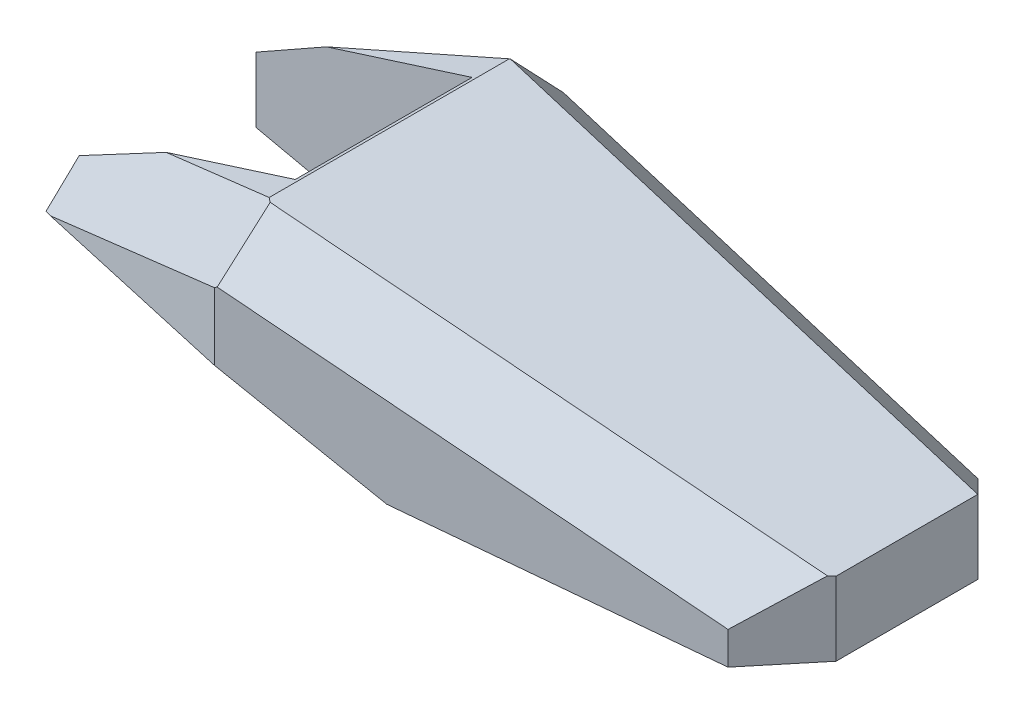
SolidWorks part; units mm, degrees
ref_plane "Front Plane" through (0, 0, 0) normal (0, 0, 1) x (1, 0, 0)
ref_plane "Top Plane" through (0, 0, 0) normal (0, 1, 0) x (1, 0, 0)
ref_plane "Right Plane" through (0, 0, 0) normal (1, 0, 0) x (0, 0, -1)
sketch "Sketch1" plane through (0, 0, 0) normal (0, 0, 1) x (1, 0, 0)
  line L0 (75, 0) -> (-75, 0)
  line L1 (-75, 0) -> (-75, 20)
  line L2 (-75, 20) -> (-30.2416, 34.2396)
  line L3 (-30.2416, 34.2396) -> (75, 15)
  line L4 (75, 15) -> (75, 0)
  point P0 (-30.2416, 34.2396)
  point P4 (0, 0)
extrude "Boss-Extrude1" add sketch "Sketch1" along normal mid plane 70
sketch "Sketch3" plane through (0, 0, 0) normal (0, -1, 0) x (1, 0, 0)
  line L0 (75, -25) -> (75, -35)
  line L1 (75, 35) -> (75, -35) construction
  line L2 (-75, 35) -> (-30.49, 35) construction
  line L3 (-75, 35) -> (75, 35) construction
  line L4 (-30.49, 35) -> (75, 25)
  line L5 (75, 35) -> (-30.49, 35)
  line L6 (75, 25) -> (75, 35)
  line L7 (-75, 35) -> (-75, 25)
  line L8 (-75, 35) -> (-75, -35) construction
  line L9 (-75, 25) -> (-30.49, 35)
  line L10 (-75, 35) -> (-30.49, 35)
  line L11 (0, 0) -> (-75, 0) construction
  line L13 (-75, 18) -> (-31, 18)
  line L14 (-31, 18) -> (-31, -18)
  line L15 (75, -35) -> (-30.49, -35)
  line L16 (-75, -35) -> (-30.49, -35) construction
  line L17 (-75, -18) -> (-31, -18)
  line L19 (-75, -35) -> (-30.49, -35)
  line L20 (-75, -25) -> (-30.49, -35)
  line L21 (-75, -35) -> (-75, -25)
  line L22 (-30.49, -35) -> (75, -25)
  line L23 (-75, 18) -> (-75, -18)
  point P5 (75, 0.2276)
  point P21 (-31, 0)
  point P24 (75, -0.2276)
  point P28 (75, 25)
  line M2 (-75, -35) -> (75, -35)
  line M3 (75, -35) -> (75, 35)
  line M4 (75, 35) -> (-75, 35)
  line M5 (-75, 35) -> (-75, -35)
  dimension "D1" = 7
extrude "Cut-Extrude1" cut sketch "Sketch3" against normal through all contours L4 M4 M3 | L22 M2 M3 | L17 L14 L13 M5 | L9 M5 M4 | L20 M5 M2
chamfer "Chamfer1" distance 10 angle 45 8 edges at (-52.745, 27.0803, -30) (-52.745, 27.0803, 30) (-52.745, 0, 30) (-52.745, 0, -30) (22.3792, 24.6198, -29.9882) (22.3792, 24.6198, 29.9882) (75, 7.5, -25) (75, 7.5, 25)
